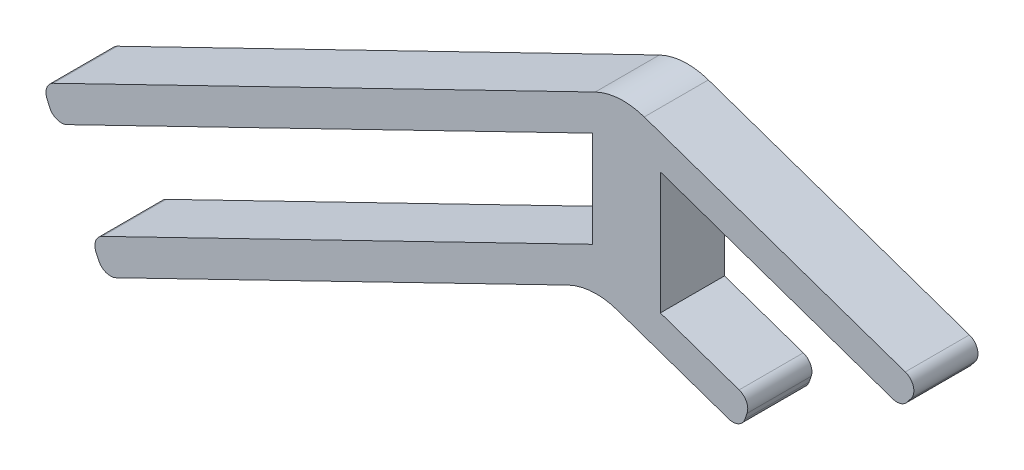
SolidWorks part; units mm, degrees
ref_plane "前基準面" through (0, 0, 0) normal (0, 0, 1) x (1, 0, 0)
ref_plane "上基準面" through (0, 0, 0) normal (0, 1, 0) x (1, 0, 0)
ref_plane "右基準面" through (0, 0, 0) normal (1, 0, 0) x (0, 0, -1)
sketch "草圖1" plane through (0, 0, 0) normal (0, 0, 1) x (1, 0, 0)
  line L0 (-89.014, -30.4602) -> (0.9286, 13.2471)
  line L1 (0.9286, 13.2471) -> (48.1809, -3.0995)
  line L2 (7.3566, 5.7327) -> (44.9361, -7.2677)
  line L3 (48.1809, -3.0995) -> (44.9361, -7.2677)
  line L4 (-87.0608, -35.0701) -> (-3.2115, 5.6762)
  line L7 (-81.4616, -47.3588) -> (-3.2115, -9.3334)
  line L8 (-79.3273, -51.8807) -> (-3.2115, -14.8925)
  line L16 (7.3566, -13.314) -> (21.5323, -18.218)
  line L17 (-1.1018, -15.6786) -> (19.8934, -22.9418)
  line L20 (7.3566, 5.7327) -> (7.3566, -13.314)
  line L21 (6.3836, 11.36) -> (7.3566, 11.36)
  line L22 (-3.2115, 5.6762) -> (-3.2115, -9.3334)
  line L24 (7.3566, 11.36) -> (7.3566, 11.0234)
  line L25 (-1.1018, -15.6786) -> (-3.2115, -14.8925)
  line L26 (-89.014, -30.4602) -> (-87.0608, -35.0701)
  line L27 (-81.4616, -47.3588) -> (-79.3273, -51.8807)
  line L28 (19.8934, -22.9418) -> (21.5323, -18.218)
  dimension "D1" = 50
  dimension "D2" = 5
  dimension "D3" = 5
  dimension "D4" = 13.5
  dimension "D5" = 100
  dimension "D6" = 18
  dimension "D7" = 5
  dimension "D8" = 5
  dimension "D9" = 135
  dimension "D10" = 87
  dimension "D11" = 15
extrude "填料-伸長1" add sketch "草圖1" along normal blind 10 contours L25 L17 L28 L16 L20 L2 L3 L1 L0 L26 L4 L22 L7 L27 L8 region at (-43.379, -9.9725, 0)
fillet "圓角1" radius 10 1 edges at (0.9286, 13.2471, 5)
fillet "圓角2" radius 10 1 edges at (-3.2115, -14.8925, 5)
fillet "圓角5" radius 2 4 edges at (19.8934, -22.9418, 5) (21.5323, -18.218, 5) (44.9361, -7.2677, 5) (48.1809, -3.0995, 5)
fillet "圓角6" radius 2 4 edges at (-79.3273, -51.8807, 5) (-81.4616, -47.3588, 5) (-87.0608, -35.0701, 5) (-89.014, -30.4602, 5)
